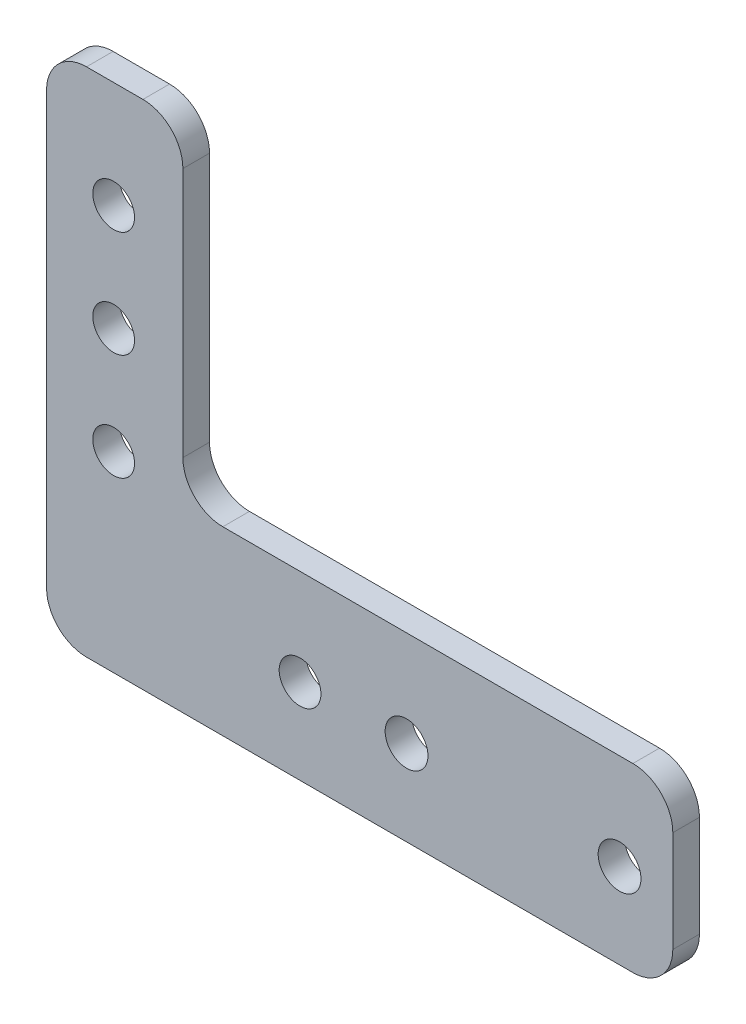
SolidWorks part; units mm, degrees
material "6061-T6 (SS)"
ref_plane "Front Plane" through (0, 0, 0) normal (0, 0, 1) x (1, 0, 0)
ref_plane "Top Plane" through (0, 0, 0) normal (0, 1, 0) x (1, 0, 0)
ref_plane "Right Plane" through (0, 0, 0) normal (1, 0, 0) x (0, 0, -1)
sketch "Sketch1" plane through (0, 0, 0) normal (0, 0, 1) x (1, 0, 0)
  line L1 (-41.275, -31.75) -> (41.275, -31.75)
  line L2 (-41.275, -31.75) -> (-41.275, 31.75)
  line L3 (-41.275, 31.75) -> (41.275, 31.75)
  line L4 (41.275, -31.75) -> (41.275, 31.75)
  line L5 (-41.275, -31.75) -> (41.275, 31.75) construction
  line L6 (-41.275, 31.75) -> (41.275, -31.75) construction
  line L7 (41.275, 31.75) -> (-17.145, 31.75)
  line L8 (41.275, 31.75) -> (41.275, -7.62)
  line L9 (41.275, -7.62) -> (-17.145, -7.62)
  line L10 (-17.145, 31.75) -> (-17.145, -7.62)
  line L11 (-41.275, -31.75) -> (-33.401, -31.75)
  line L12 (-41.275, -31.75) -> (-41.275, 31.75)
  line L13 (-41.275, 31.75) -> (-33.401, 31.75)
  line L14 (-33.401, -31.75) -> (-33.401, 31.75)
  line L15 (-33.401, -31.75) -> (41.275, -31.75)
  line L16 (-33.401, -31.75) -> (-33.401, -29.21)
  line L17 (-33.401, -29.21) -> (41.275, -29.21)
  line L18 (41.275, -31.75) -> (41.275, -29.21)
  circle A0 centre (-25.4, -19.05) radius 2.4892
  circle A1 centre (-25.4, -6.35) radius 2.4892
  circle A2 centre (-25.4, 6.35) radius 2.4892
  circle A3 centre (-25.4, 19.05) radius 2.4892
  circle A4 centre (-3.175, -19.05) radius 2.4892
  circle A5 centre (9.525, -19.05) radius 2.5527
  circle A7 centre (34.925, -19.05) radius 2.5527
  point P0 (0, 0)
  dimension "D7" = 4.9784
  dimension "D18" = 5.1054
  dimension "D15" = 50.8
  dimension "D14" = 22.225
  dimension "D1" = 82.55
  dimension "D2" = 63.5
  dimension "D3" = 24.13
  dimension "D4" = 24.13
  dimension "D5" = 7.874
  dimension "D6" = 63.5
  dimension "D8" = 15.875
  dimension "D9" = 12.7
  dimension "D10" = 12.7
  dimension "D11" = 12.7
  dimension "D12" = 12.7
  dimension "D13" = 25.4
  dimension "D16" = 2.54
extrude "Boss-Extrude1" add sketch "Sketch1" along normal blind 3.175 contours L14 L17 L4 L9 L10 L3 A5 A4 A3 A2 A1 A0 | A0 region at (-4.1144, -9.8474, 0) region at (-25.4, -19.05, 0)
fillet "Fillet1" radius 4.7625 6 edges at (-33.401, 31.75, 1.5875) (-17.145, 31.75, 1.5875) (-17.145, -7.62, 1.5875) (41.275, -7.62, 1.5875) (41.275, -29.21, 1.5875) (-33.401, -29.21, 1.5875)
